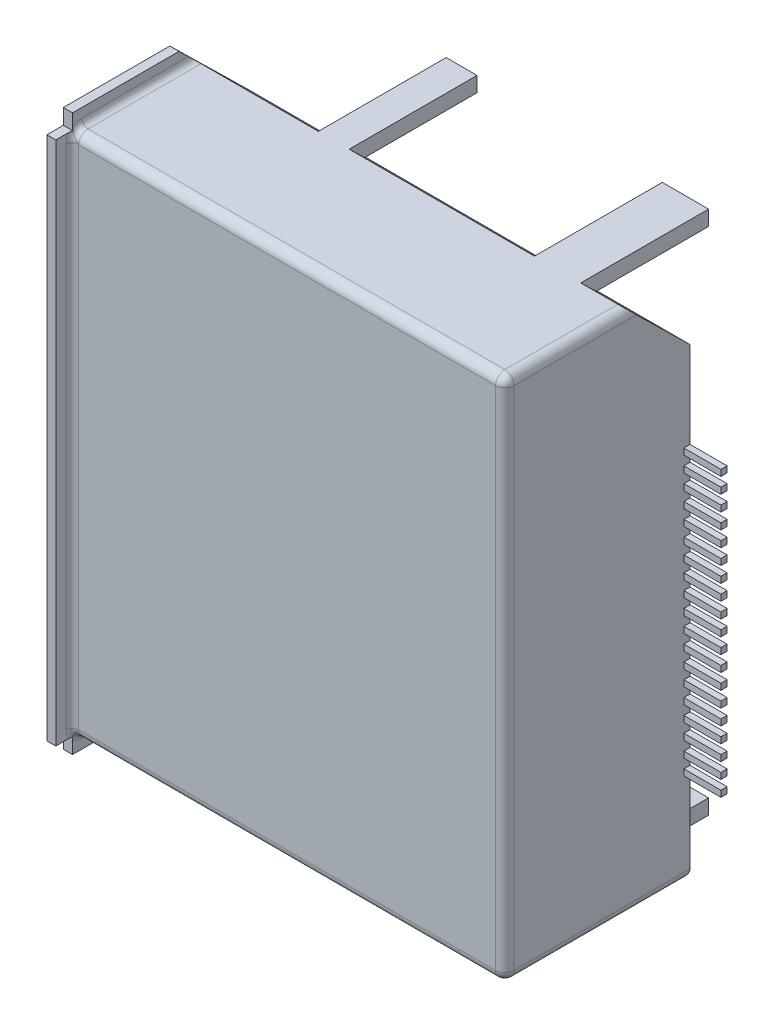
SolidWorks part; units mm, degrees
ref_plane "前视基准面" through (0, 0, 0) normal (0, 0, 1) x (1, 0, 0)
ref_plane "上视基准面" through (0, 0, 0) normal (0, 1, 0) x (1, 0, 0)
ref_plane "右视基准面" through (0, 0, 0) normal (1, 0, 0) x (0, 0, -1)
sketch "草图1" plane through (0, 0, 0) normal (0, 0, 1) x (1, 0, 0)
  line L1 (0, 0) -> (14.3, 0)
  line L2 (0, 0) -> (0, -17)
  line L3 (0, -17) -> (14.3, -17)
  line L4 (14.3, 0) -> (14.3, -17)
  dimension "D1" = 14.3
  dimension "D2" = 17
extrude "凸台-拉伸1" add sketch "草图1" along normal blind 6
sketch "草图3" plane through (14.3, 0, 0) normal (1, 0, 0) x (0, 0, -1)
  line L0 (0, -17) -> (0, 0) construction
  line L1 (0, -14) -> (-0.2, -14)
  line L2 (0, -14) -> (0, -13.8)
  line L3 (0, -13.8) -> (-0.2, -13.8)
  line L4 (-0.2, -14) -> (-0.2, -13.8)
  line L5 (-6, -17) -> (0, -17) construction
  dimension "D1" = 0.2
  dimension "D2" = 0.2
  dimension "D3" = 3
extrude "凸台-拉伸3" add sketch "草图3" along normal blind 1.2
pattern_linear "阵列(线性)1" count 19 spacing 0.5 along (0, 1, 0) of "凸台-拉伸3"
sketch "草图4" plane through (0, 0, 6) normal (0, 0, 1) x (1, 0, 0)
  line L0 (0, -8.5) -> (5.4419, -8.5) construction
  line L1 (0, 0) -> (0.3, 0)
  line L2 (0, 0) -> (0, 0.5)
  line L3 (0, 0.5) -> (0.3, 0.5)
  line L4 (0.3, 0) -> (0.3, 0.5)
  line L5 (0, 0) -> (0, -17) construction
  line L6 (0.3, -17) -> (0.3, -17.5)
  line L7 (0, -17.5) -> (0.3, -17.5)
  line L8 (0, -17) -> (0, -17.5)
  line L9 (0, -17) -> (0.3, -17)
  dimension "D1" = 0.5
  dimension "D2" = 0.3
extrude "凸台-拉伸4" add sketch "草图4" against normal up to surface (6 mm away) up to face at (14.5275, -9.4375, 0)
sketch "草图5" plane through (0, -17, 0) normal (0, -1, 0) x (1, 0, 0)
  line L1 (0, 6) -> (0.2889, 6)
  line L2 (0, 6) -> (0, 6.5312)
  line L3 (0, 6.5312) -> (0.2889, 6.5312)
  line L4 (0.2889, 6) -> (0.2889, 6.5312)
extrude "凸台-拉伸5" add sketch "草图5" against normal up to surface (17 mm away) up to face at (10.8, 0, 2.25)
sketch "草图6" plane through (0, 0, 0) normal (-1, 0, 0) x (0, 0, 1)
  line L0 (0.8143, -1.577) -> (1.8143, -0.577)
  line L1 (1.8143, -0.577) -> (5.0869, -0.577)
  line L2 (0.8143, -1.577) -> (0.8143, -16.5739)
  line L3 (0.8143, -16.5739) -> (5.0869, -16.5739)
  line L4 (5.0869, -0.577) -> (5.0869, -16.5739)
  point P0 (0.8143, -0.577)
  dimension "D3" = 1
extrude "切除-拉伸1" cut sketch "草图6" against normal blind 10
sketch "草图8" plane through (10, 0, 0) normal (-1, 0, 0) x (0, 0, 1)
  line L1 (2.4993, -2.7263) -> (3.3827, -2.7263)
  line L2 (2.4993, -2.7263) -> (2.4993, -14.6574)
  line L3 (2.4993, -14.6574) -> (3.3827, -14.6574)
  line L4 (3.3827, -2.7263) -> (3.3827, -14.6574)
extrude "凸台-拉伸6" add sketch "草图8" along normal blind 5.2
sketch "草图11" plane through (14.3, 0, 0) normal (1, 0, 0) x (0, 0, -1)
  line L0 (-2.745, 0.6907) -> (0.4405, -2.4301)
  line L2 (0.4405, -2.4301) -> (0.4405, 0.6907)
  line L3 (0.4405, 0.6907) -> (-2.745, 0.6907)
extrude "切除-拉伸4" cut sketch "草图11" against normal through all
sketch "草图12" plane through (0, 0, 0) normal (0, 0, -1) x (-1, 0, 0)
  line L0 (-0.3, -17) -> (-14.3, -17) construction
  line L1 (-12.8, -17) -> (-11.3, -17)
  line L2 (-12.8, -17) -> (-12.8, -16.5136)
  line L3 (-12.8, -16.5136) -> (-11.3, -16.5136)
  line L4 (-11.3, -17) -> (-11.3, -16.5136)
  line L5 (-14.3, -17) -> (-14.3, -14) construction
  line L6 (-5.3, -17) -> (-4.3, -17)
  line L7 (-5.3, -17) -> (-5.3, -16.5136)
  line L8 (-5.3, -16.5136) -> (-4.3, -16.5136)
  line L9 (-4.3, -17) -> (-4.3, -16.5136)
  line L10 (-11.6083, -8.5) -> (-1.0437, -8.5) construction
  line L11 (-4.3, 0) -> (-4.3, -0.4864)
  line L12 (-5.3, -0.4864) -> (-4.3, -0.4864)
  line L13 (-5.3, 0) -> (-5.3, -0.4864)
  line L14 (-5.3, 0) -> (-4.3, 0)
  line L15 (-11.3, 0) -> (-11.3, -0.4864)
  line L16 (-12.8, -0.4864) -> (-11.3, -0.4864)
  line L17 (-12.8, 0) -> (-12.8, -0.4864)
  line L18 (-12.8, 0) -> (-11.3, 0)
  dimension "D1" = 10
  dimension "D2" = 1
  dimension "D3" = 1.5
  dimension "D4" = 3
  dimension "D5" = 8.5
extrude "凸台-拉伸7" add sketch "草图12" along normal blind 2.1 and the other way blind 5.2
sketch "草图13" plane through (0, 0, 0) normal (0, 0, -1) x (-1, 0, 0)
  line L0 (-9.3499, -8.7574) -> (-2.5109, -8.7574) construction
  line L1 (0, -1.9985) -> (0, -17.5) construction
  circle A0 centre (-4.5, -8.7574) radius 0.6
  dimension "D1" = 1.2
  dimension "D2" = 4.5
extrude "凸台-拉伸8" add sketch "草图13" along normal blind 2
fillet "圆角1" radius 0.3 8 edges at (14.3, 0, 4.02) (14.3, -17, 3) (14.3, -8.5, 6)
fillet "圆角3" radius 0.2 5 edges at (0.3, -16.9121, 0.0879) (0.3, -16.9121, 5.9121) (0.3, -0.0879, 5.9121)
fillet "圆角4" radius 0.2 1 edges at (0.2889, -8.5, 6)
